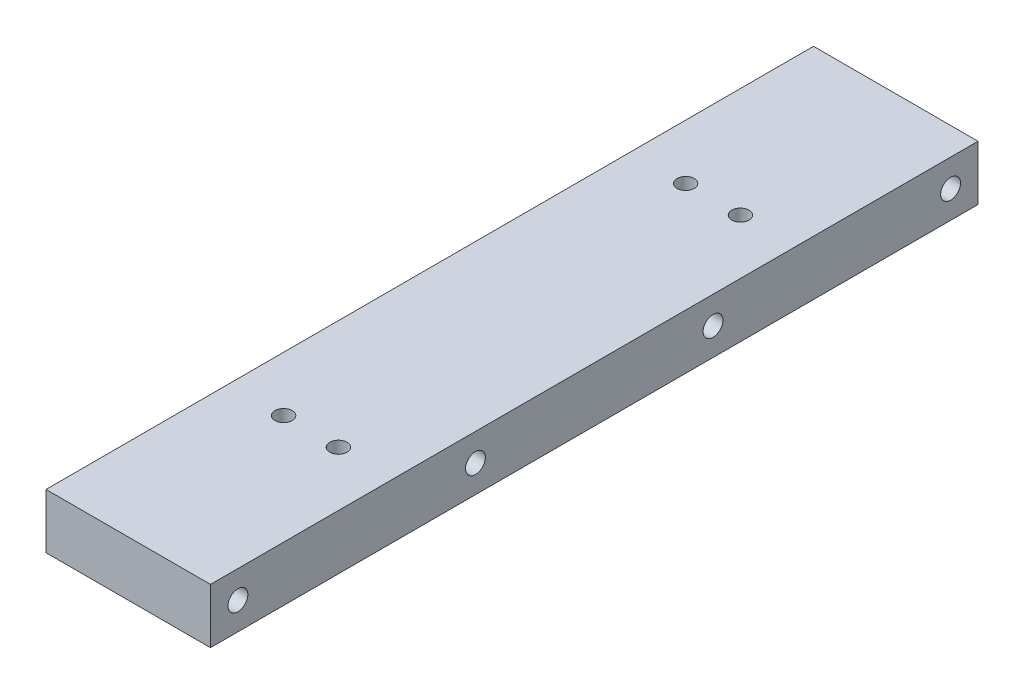
SolidWorks part; units mm, degrees
ref_plane "Front Plane" through (0, 0, 0) normal (0, 0, 1) x (1, 0, 0)
ref_plane "Top Plane" through (0, 0, 0) normal (0, 1, 0) x (1, 0, 0)
ref_plane "Right Plane" through (0, 0, 0) normal (1, 0, 0) x (0, 0, -1)
sketch "Sketch2" plane through (0, 0, 0) normal (0, 1, 0) x (1, 0, 0)
  line L0 (0, 0) -> (28.575, 0)
  line L1 (28.575, 0) -> (28.575, 133.35)
  line L2 (28.575, 133.35) -> (0, 133.35)
  line L3 (0, 133.35) -> (0, 0)
  dimension "D1" = 133.35
  dimension "D2" = 28.575
extrude "Boss-Extrude1" add sketch "Sketch2" along normal blind 9.525
sketch "Sketch3" plane through (28.575, 0, 0) normal (1, 0, 0) x (0, 0, -1)
  line L0 (0, 9.525) -> (0, 0) construction
  line L1 (0, 9.525) -> (133.35, 9.525) construction
  point P0 (4.7625, 4.7625)
  dimension "D1" = 4.7625
  dimension "D2" = 4.7625
sketch "Sketch4" plane through (28.575, 0, 0) normal (1, 0, 0) x (0, 0, -1)
  point P0 (4.7625, 4.7625)
hole_wizard "#5 Clearance Hole1" positions "Sketch4" profile "Sketch5" hole size "#5" standard "ANSI Inch" end condition through all
sketch "Sketch5" plane through (28.575, 4.7625, -4.7625) normal (0, 1, 0) x (0, 0, -1)
  line L0 (0, 0) -> (0, 28.575)
  line L1 (0, 28.575) -> (1.7272, 28.575)
  line L2 (1.7272, 28.575) -> (1.7272, 0)
  line L5 (1.7272, 0) -> (0, 0)
  line L11 (0, -6.35) -> (0, 107.95) construction
  dimension "Thru Hole Dia." = 3.4544
  dimension "Thru Hole Depth" = 28.575
pattern_linear "LPattern1" count 4 spacing 41.275 along (0, 0, -1) of "#5 Clearance Hole1"
sketch "Sketch8" plane through (0, 0, 0) normal (0, -1, 0) x (1, 0, 0)
  line L0 (0, 0) -> (14.2875, 0)
  line L1 (0, 0) -> (28.575, 0) construction
  line L2 (28.575, -133.35) -> (0, -133.35) construction
  line L3 (0, -133.35) -> (0, 0) construction
  line L4 (28.575, 0) -> (28.575, -133.35) construction
  circle A0 centre (9.525, -31.75) radius 1.5
  circle A1 centre (9.525, -101.6) radius 1.5
  circle A2 centre (19.05, -101.6) radius 1.5
  circle A3 centre (19.05, -31.75) radius 1.5
  point P5 (9.525, -31.75)
  point P6 (9.525, -101.6)
  point P15 (19.05, -31.75)
  point P16 (19.05, -101.6)
  dimension "D5" = 3
  dimension "D6" = 3
  dimension "D11" = 3
  dimension "D12" = 3
  dimension "D1" = 31.75
  dimension "D2" = 31.75
  dimension "D3" = 9.525
  dimension "D4" = 9.525
  dimension "D7" = 9.525
  dimension "D8" = 9.525
  dimension "D9" = 31.75
  dimension "D10" = 31.75
extrude "Cut-Extrude2" cut sketch "Sketch8" against normal through all contours A0 | A1 | A2 | A3 region at (9.525, 0, -31.75) region at (9.525, 0, -101.6)
